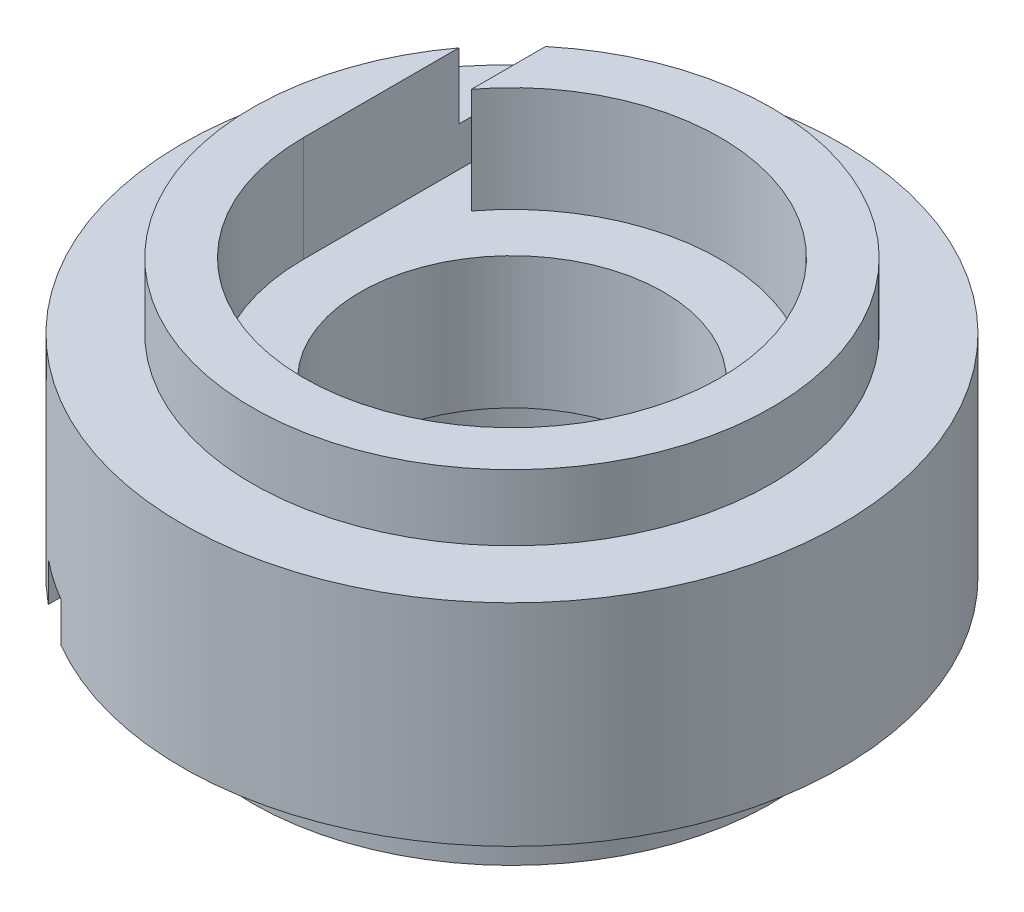
SolidWorks part; units mm, degrees
other "Markup1"
sketch "Sketch14" plane through (31.75, -16.51, 39.3443) normal (0.2842, -0.9484, 0.1408) x (0.2076, -0.0825, -0.9747)
ref_plane "Front Plane" through (0, 0, 0) normal (0, 0, 1) x (1, 0, 0)
ref_plane "Top Plane" through (0, 0, 0) normal (0, 1, 0) x (1, 0, 0)
ref_plane "Right Plane" through (0, 0, 0) normal (1, 0, 0) x (0, 0, -1)
sketch "Sketch1" plane through (0, 0, 0) normal (0, 1, 0) x (1, 0, 0)
  circle A0 centre (0, 0) radius 31.75
  circle A1 centre (0, 0) radius 14.605
  dimension "D1" = 63.5
  dimension "D2" = 29.21
extrude "Boss-Extrude1" add sketch "Sketch1" along normal mid plane 33.02
sketch "Sketch2" plane through (0, 16.51, 0) normal (0, 1, 0) x (1, 0, 0)
  line L0 (-20.066, 0) -> (-20.066, 24.6052)
  line L1 (-16.002, 12.107) -> (-16.002, 27.4226)
  arc A0 (-20.066, 0) -> (-16.002, 12.107) centre (0, 0) ccw
  circle A1 centre (0, 0) radius 31.75 construction
  arc A2 (-16.002, 27.4226) -> (-20.066, 24.6052) centre (0, 0) ccw
  dimension "D1" = 4.064
extrude "Cut-Extrude1" cut sketch "Sketch2" against normal blind 10.16
sketch "Sketch13" plane through (0, 16.51, 0) normal (0, 1, 0) x (1, 0, 0)
  circle A1 centre (0, 0) radius 25.019
  circle A2 centre (0, 0) radius 31.75
  arc A3 (-20.066, 24.6052) -> (-16.002, 27.4226) centre (0, 0) ccw construction
  dimension "D1" = 50.038
extrude "Cut-Extrude2" cut sketch "Sketch13" against normal blind 6.35
sketch "Sketch5" plane through (0, 0, 0) normal (0, 1, 0) x (1, 0, 0)
  line L0 (0, -39.3443) -> (0, 40.2571) construction
  line L1 (0, -22.352) -> (0, 22.352) construction
ref_axis "Axis1" through (34.925, 0, 0) along (-1, 0, 0)
sketch "Sketch9" plane through (0, 0, 0) normal (0, 0, 1) x (1, 0, 0)
  line L0 (0, -22.352) -> (0, 22.352) construction
  line L1 (-20.066, 3.81) -> (-14.478, 3.81)
  line L2 (-20.066, 3.81) -> (-20.066, 0)
  line L3 (-20.066, 0) -> (-14.478, 0)
  line L4 (-14.478, 3.81) -> (-14.478, 0)
  point P5 (-14.478, 1.905)
  dimension "D1" = 3.81
  dimension "D2" = 14.478
sketch "Sketch12" plane through (0, 6.35, 0) normal (0, 1, 0) x (1, 0, 0)
  circle A0 centre (0, 0) radius 14.605
  circle A1 centre (0, 0) radius 14.605 construction
curve "Helix/Spiral2" pitch 3.302 height 2.9619 turns 0.897
pattern_circular "CirPattern1" count 2 every 180 about axis through (34.925, 0, 0) along (-1, 0, 0) of "Cut-Extrude2", "Cut-Extrude1"
